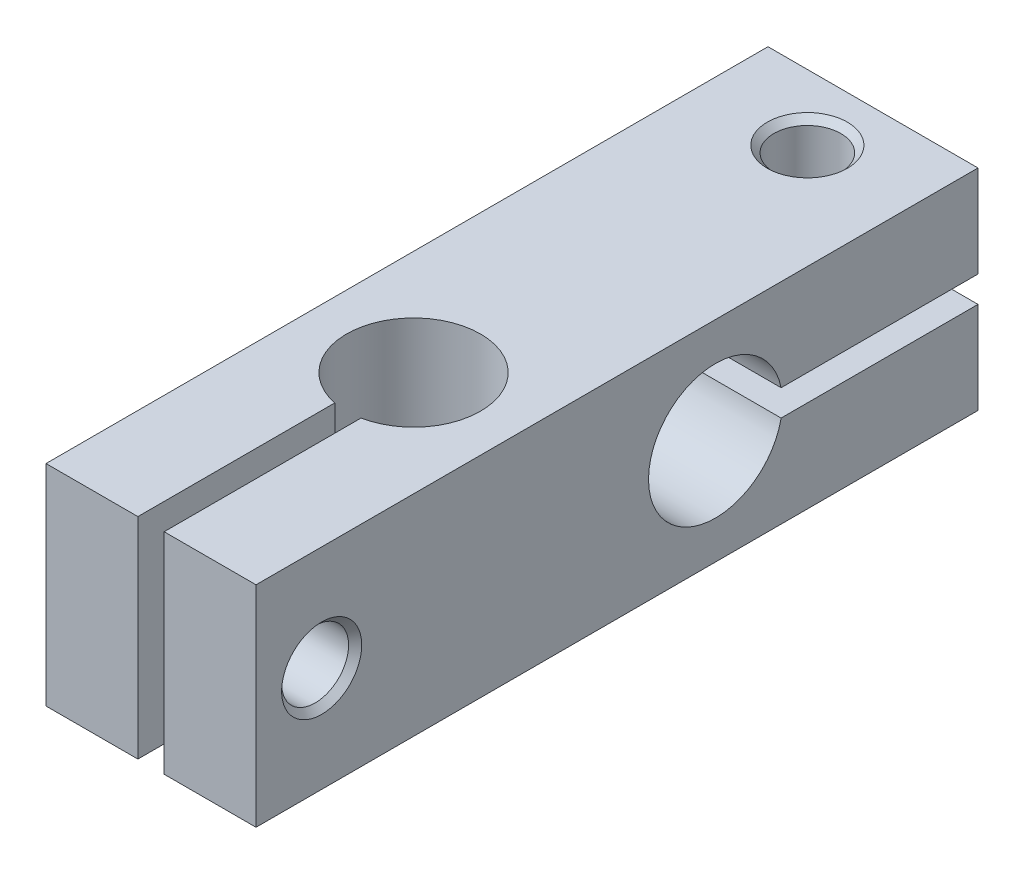
SolidWorks part; units mm, degrees
material "6063-T6"
ref_plane "Front Plane" through (0, 0, 0) normal (0, 0, 1) x (1, 0, 0)
ref_plane "Top Plane" through (0, 0, 0) normal (0, 1, 0) x (1, 0, 0)
ref_plane "Right Plane" through (0, 0, 0) normal (1, 0, 0) x (0, 0, -1)
sketch "Sketch1" plane through (0, 0, 0) normal (0, 0, 1) x (1, 0, 0)
  line L1 (8, -8) -> (-8, -8)
  line L2 (8, -8) -> (8, 8)
  line L3 (8, 8) -> (-8, 8)
  line L4 (-8, -8) -> (-8, 8)
  line L5 (8, -8) -> (-8, 8) construction
  line L6 (8, 8) -> (-8, -8) construction
  point P0 (0, 0)
  dimension "D1" = 16
  dimension "D2" = 16
extrude "Base" add sketch "Sketch1" along normal blind 55
sketch "Sketch2" plane through (0, 8, 0) normal (0, 1, 0) x (1, 0, 0)
  line L0 (-1, -55) -> (-1, -39)
  line L1 (8, -55) -> (-8, -55) construction
  line L2 (1, -55) -> (1, -39)
  line L3 (0, 0) -> (0, -9.2456) construction
  line L4 (-1, -39) -> (1, -39)
  line M6 (-8, -55) -> (8, -55)
  dimension "D1" = 16
  dimension "D3" = 2
extrude "RodSlot" cut sketch "Sketch2" against normal through all contours L0 L2 M6 region at (0, 8, 47)
hole_wizard "Ø5.1 (5.1) free hole for screw" positions "Sketch7" profile "Sketch8" hole size "Ø5.1" standard "ANSI Metric"
sketch "Sketch7" plane through (8, 0, 0) normal (1, 0, 0) x (0, 0, -1)
  line L0 (-55, -8) -> (-55, 8) construction
  point P0 (-50, 0)
  dimension "D1" = 5
sketch "Sketch8" plane through (8, 0, 50) normal (0, 1, 0) x (0, 0, -1)
  line L0 (0, 0) -> (0, 8.5562)
  line L1 (0, 8.5562) -> (2.55, 7.5)
  line L2 (2.55, 7.5) -> (2.55, 0.5)
  line L3 (2.55, 0.5) -> (3.05, 0)
  line L5 (3.05, 0) -> (0, 0)
  line L6 (-2.55, 0.5) -> (-3.05, 0) construction
  line L10 (0, 8.5562) -> (-2.55, 7.5) construction
  line L11 (0, -6.35) -> (0, 107.95) construction
  dimension "Hole Dia." = 5.1
  dimension "Hole Depth" = 7.5
  dimension "Near C'Sink Dia." = 6.1
  dimension "Near C'Sink Angle" = 90
  dimension "Drill Angle" = 135
hole_wizard "M5x0.8 Tapped Hole for rod screw" positions "Sketch4" profile "Sketch5" tap size "M5x0.8" standard "ANSI Metric"
sketch "Sketch4" plane through (-8, 0, 0) normal (-1, 0, 0) x (0, 0, 1)
  point P0 (50, 0)
cosmetic thread "Hole Thread1" parameters "D1"=7, "D2"=5
sketch "Sketch5" plane through (-8, 0, 50) normal (0, 1, 0) x (0, 0, 1)
  line L0 (0, 0) -> (0, 8.9)
  line L1 (0, 8.9) -> (2.1, 7.6382)
  line L2 (2.1, 7.6382) -> (2.1, 0)
  line L5 (2.1, 0) -> (0, 0)
  line L10 (0, 8.9) -> (-2.1, 7.6382) construction
  line L11 (0, -6.35) -> (0, 107.95) construction
  dimension "Tap Drill Dia." = 4.2
  dimension "Tap Drill Depth" = 8.9
  dimension "Drill Angle" = 118
hole_wizard "Ø10.2 (10.2) Rod Hole" positions "Sketch11" profile "Sketch12" hole size "Ø10.2" standard "ANSI Metric" end condition through all
sketch "Sketch11" plane through (0, 8, 0) normal (0, 1, 0) x (1, 0, 0)
  line L1 (8, -55) -> (1, -55) construction
  point P0 (0, -35)
  dimension "D1" = 20
sketch "Sketch12" plane through (0, 8, 35) normal (1, 0, 0) x (0, 0, 1)
  line L0 (0, 0) -> (0, 16)
  line L1 (0, 16) -> (5.1, 16)
  line L2 (5.1, 16) -> (5.1, 0)
  line L5 (5.1, 0) -> (0, 0)
  line L11 (0, -6.35) -> (0, 107.95) construction
  dimension "Thru Hole Dia." = 10.2
  dimension "Thru Hole Depth" = 16
sketch "Sketch13" plane through (-8, 0, 0) normal (-1, 0, 0) x (0, 0, 1)
  line L0 (0, 8) -> (0, -8) construction
  line L1 (0, 1) -> (20, 1)
  line L2 (0, 1) -> (0, -1)
  line L3 (0, -1) -> (20, -1)
  line L4 (20, 1) -> (20, -1)
  point P6 (0, 0)
  dimension "D1" = 2
  dimension "D2" = 20
extrude "Rod2Slot" cut sketch "Sketch13" against normal through all
hole_wizard "Ø10.2 (10.2) Rod2 Hole" positions "Sketch14" profile "Sketch15" hole size "Ø10.2" standard "ANSI Metric" end condition through all
sketch "Sketch14" plane through (-8, 0, 0) normal (-1, 0, 0) x (0, 1, 0)
  point P0 (0, -20)
  dimension "D1" = 20
sketch "Sketch15" plane through (-8, 0, 20) normal (0, 1, 0) x (0, 0, 1)
  line L0 (0, 0) -> (0, 16)
  line L1 (0, 16) -> (5.1, 16)
  line L2 (5.1, 16) -> (5.1, 0)
  line L5 (5.1, 0) -> (0, 0)
  line L11 (0, -6.35) -> (0, 107.95) construction
  dimension "Thru Hole Dia." = 10.2
  dimension "Thru Hole Depth" = 16
hole_wizard "Ø5.1 (5.1) Diameter Hole1" positions "Sketch16" profile "Sketch17" hole size "Ø5.1" standard "ANSI Metric"
sketch "Sketch16" plane through (0, 8, 0) normal (0, 1, 0) x (0, 0, -1)
  line L1 (0, -8) -> (0, 8) construction
  point P0 (-5, 0)
  dimension "D1" = 5
sketch "Sketch17" plane through (0, 8, 5) normal (1, 0, 0) x (0, 0, 1)
  line L0 (0, 0) -> (0, 8.5562)
  line L1 (0, 8.5562) -> (2.55, 7.5)
  line L2 (2.55, 7.5) -> (2.55, 0.5)
  line L3 (2.55, 0.5) -> (3.05, 0)
  line L5 (3.05, 0) -> (0, 0)
  line L6 (-2.55, 0.5) -> (-3.05, 0) construction
  line L10 (0, 8.5562) -> (-2.55, 7.5) construction
  line L11 (0, -6.35) -> (0, 107.95) construction
  dimension "Hole Dia." = 5.1
  dimension "Hole Depth" = 7.5
  dimension "Near C'Sink Dia." = 6.1
  dimension "Near C'Sink Angle" = 90
  dimension "Drill Angle" = 135
hole_wizard "M5x0.8 Tapped Hole1" positions "Sketch19" profile "Sketch20" tap size "M5x0.8" standard "ANSI Metric"
sketch "Sketch19" plane through (0, -8, 0) normal (0, -1, 0) x (-1, 0, 0)
  line L0 (8, 0) -> (-8, 0) construction
  point P0 (0, -5)
  dimension "D1" = 5
sketch "Sketch20" plane through (0, -8, 5) normal (1, 0, 0) x (0, 0, -1)
  line L0 (0, 0) -> (0, 8.9)
  line L1 (0, 8.9) -> (2.1, 7.6382)
  line L2 (2.1, 7.6382) -> (2.1, 0)
  line L5 (2.1, 0) -> (0, 0)
  line L10 (0, 8.9) -> (-2.1, 7.6382) construction
  line L11 (0, -6.35) -> (0, 107.95) construction
  dimension "Tap Drill Dia." = 4.2
  dimension "Tap Drill Depth" = 8.9
  dimension "Drill Angle" = 118
cosmetic thread "Hole Thread2" parameters "D1"=7, "D2"=5
equation "\"D2@Sketch1\"=\"D1@Sketch1\""
